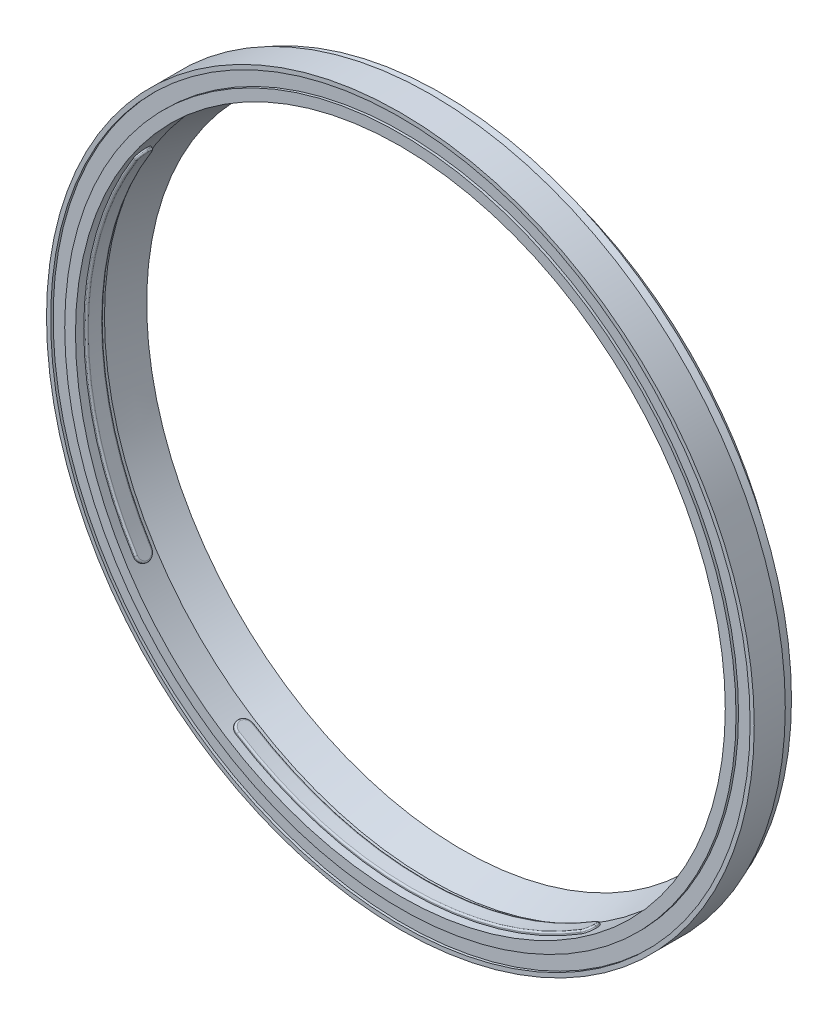
SolidWorks part; units mm, degrees
material "TPU-95A"
ref_plane "Front Plane" through (0, 0, 0) normal (0, 0, 1) x (1, 0, 0)
ref_plane "Top Plane" through (0, 0, 0) normal (0, 1, 0) x (1, 0, 0)
ref_plane "Right Plane" through (0, 0, 0) normal (1, 0, 0) x (0, 0, -1)
sketch "Sketch1" plane through (0, 0, 0) normal (1, 0, 0) x (0, 0, -1)
  line L0 (0, 0) -> (57.7495, 0) construction
  line L1 (3.75, 42.75) -> (3.75, 42.25)
  line L2 (0, 42.75) -> (3.75, 42.75)
  line L3 (3.75, 42.25) -> (5, 42.25) construction
  line L4 (5, 42.25) -> (3.75, 41.8416)
  line L5 (3.75, 41.8416) -> (3.75, 42.25)
  line L6 (7.5, 39) -> (7.5, 38.15)
  line L7 (7.5, 38.15) -> (3.5, 39.25)
  line L8 (3.5, 39.25) -> (0, 39.25)
  line L9 (0, 39.25) -> (0, 40.55)
  line L10 (5, 42.25) -> (5, 41.4084)
  line L11 (5, 41.4084) -> (3.973, 41.0729)
  line L12 (3.957, 40.8896) -> (7.5, 39)
  line L13 (0, 42.25) -> (0.3, 42.25)
  line L14 (0.3, 42.25) -> (0.3, 40.55)
  line L15 (0.3, 40.55) -> (0, 40.55)
  line L16 (0, 42.25) -> (0, 42.75)
  arc A0 (3.973, 41.0729) -> (3.957, 40.8896) centre (4.0041, 40.9778) ccw
  point P7 (3.75, 41)
  dimension "D11" = 82
  dimension "D12" = 0.1
  dimension "D1" = 85.5
  dimension "D2" = 3.5
  dimension "D3" = 3.75
  dimension "D4" = 5
  dimension "D5" = 0.5
  dimension "D6" = 76.3
  dimension "D7" = 78
  dimension "D8" = 0.8
  dimension "D9" = 3.5
  dimension "D10" = 7.5
  dimension "D13" = 0.5
  dimension "D14" = 1.3
  dimension "D15" = 0.3
  dimension "D16" = 78.5
  dimension "D17" = 84.5
revolve "Revolve1" add sketch "Sketch1" angle 360 about L0
ref_plane "Plane1" through (0, 0, -1) normal (0, 0, 1) x (1, 0, 0)
sketch "Sketch2" plane through (0, 0, -1) normal (0, 0, 1) x (1, 0, 0)
  line L0 (0, 0) -> (0, 24.3515) construction
  line L1 (-21.6934, 32.7102) -> (-21.5, 32.4185)
  line L2 (21.6934, 32.7102) -> (21.5, 32.4185)
  arc A0 (21.5, 32.4185) -> (-21.5, 32.4185) centre (0, 0) ccw
  arc A1 (21.6934, 32.7102) -> (-21.6934, 32.7102) centre (0, 0) ccw
  circle A2 centre (0, 0) radius 39.25 construction
  dimension "D1" = 38.9
  dimension "D2" = 43
extrude "Boss-Extrude1" add sketch "Sketch2" against normal blind 2
fillet "Fillet1" radius 1 4 edges at (-21.5967, 32.5644, -3) (-21.5967, 32.5644, -1) (21.5967, 32.5644, -3) (21.5967, 32.5644, -1)
fillet "Fillet2" radius 0.2 6 edges at (-21.1862, 32.6245, -1.2191) (-21.317, 32.5391, -2.6247) (0, 38.9, -3) (21.1862, 32.6245, -2.7809) (21.317, 32.5391, -1.3753) (0, 38.9, -1)
pattern_circular "CirPattern1" count 4 over 360 about axis through (0, 0, 0) along (0, 0, 1) of "Boss-Extrude1", "Fillet1", "Fillet2"
